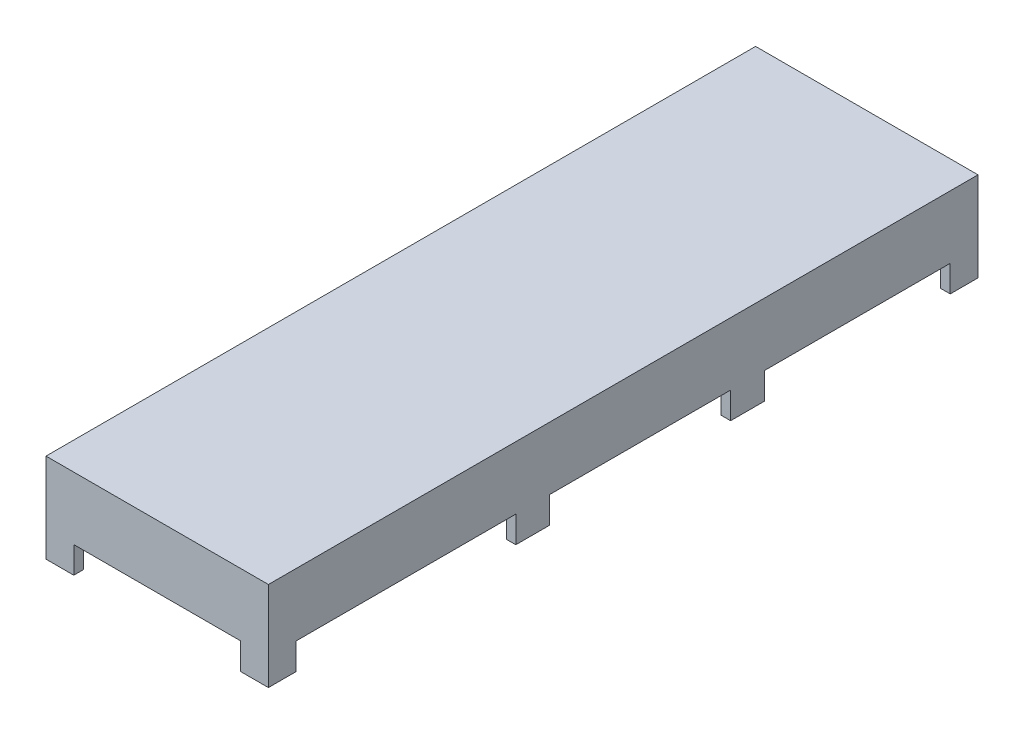
SolidWorks part; units mm, degrees
note: The reader was unsure of these and kept them because the rebuilt part matched: shared geometry of "草图2<5>".
material "6061 合金"
ref_plane "前视基准面" through (0, 0, 0) normal (0, 0, 1) x (1, 0, 0)
ref_plane "上视基准面" through (0, 0, 0) normal (0, 1, 0) x (1, 0, 0)
ref_plane "右视基准面" through (0, 0, 0) normal (1, 0, 0) x (0, 0, -1)
other "Configuration Table"
sketch "草图2" plane through (0, 0, 0) normal (0, 1, 0) x (1, 0, 0)
  line L1 (0, 0) -> (9.215, 0)
  line L2 (0, 0) -> (0, 29.4)
  line L3 (0, 29.4) -> (9.215, 29.4)
  line L4 (9.215, 0) -> (9.215, 29.4)
  line L5 (0, 0) -> (9.215, 0)
  line L6 (0, 0) -> (0, 29.4)
  line L7 (0, 29.4) -> (9.215, 29.4)
  line L8 (9.215, 0) -> (9.215, 29.4)
  line L9 (0.4, 0.4) -> (8.82, 0.4)
  line L10 (0.4, 0.4) -> (0.4, 29)
  line L11 (0.4, 29) -> (8.82, 29)
  line L12 (8.82, 0.4) -> (8.82, 29)
  dimension "D1" = 9.215
  dimension "D2" = 29.4
extrude "凸台-拉伸1" add sketch "草图2" along normal blind 3.7 contours L3 L4 L1 L2
extrude "切除-拉伸2" cut sketch "草图2<5>" along normal blind 3.3 contours L9 L12 L11 L10
sketch "草图2<5>" plane through (0, 0, 0) normal (0, 1, 0) x (1, 0, 0) same geometry as "草图2"
sketch "草图3" plane through (0, 0, 0) normal (0, 0, 1) x (1, 0, 0)
  line L0 (0, 0) -> (1.15, 0)
  line L1 (0, 0) -> (9.215, 0) construction
  line L2 (1.15, 0) -> (1.15, 1.1)
  line L4 (9.215, 0) -> (8.065, 0)
  line L5 (8.065, 0) -> (8.065, 1.1)
  line L6 (8.065, 1.1) -> (1.15, 1.1)
  line L7 (1.15, 0) -> (8.065, 0)
  dimension "D1" = 1.15
  dimension "D2" = 1.15
  dimension "D3" = 1.1
extrude "切除-拉伸7" cut sketch "草图3" against normal blind 0.4 and the other way through all contours L2 L6 L5
sketch "草图8" plane through (0, 0, -29.4) normal (0, 0, -1) x (-1, 0, 0)
  line L1 (-9.215, 0) -> (-8.065, 0)
  line L2 (-8.065, 0) -> (-8.065, 1.1)
  line L3 (-8.065, 1.1) -> (-1.15, 1.1)
  line L4 (-1.15, 1.1) -> (-1.15, 0)
  line L5 (-1.15, 0) -> (0, 0)
extrude "切除-拉伸11" cut sketch "草图8" against normal blind 0.4 and the other way through all flip side to cut contours L1 L2 L3 L4 L5
sketch "草图11" plane through (9.215, 0, 0) normal (1, 0, 0) x (0, 0, -1)
  line L0 (0, 0) -> (1.15, 0)
  line L1 (0, 0) -> (29.4, 0) construction
  line L2 (1.15, 0) -> (1.15, 1.1)
  line L3 (1.15, 1.1) -> (10.25, 1.1)
  line L4 (10.25, 1.1) -> (10.25, 0)
  line L5 (10.25, 0) -> (11.65, 0)
  line L6 (11.65, 0) -> (11.65, 1.1)
  line L7 (11.65, 1.1) -> (19.15, 1.1)
  line L8 (19.15, 1.1) -> (19.15, 0)
  line L9 (19.15, 0) -> (20.55, 0)
  line L10 (20.55, 0) -> (20.55, 1.1)
  line L11 (20.55, 1.1) -> (28.25, 1.1)
  line L12 (28.25, 1.1) -> (28.25, 0)
  line L13 (28.25, 0) -> (29.4, 0)
  dimension "D1" = 1.15
  dimension "D2" = 1.4
  dimension "D3" = 1.4
  dimension "D4" = 1.15
  dimension "D5" = 9.1
  dimension "D6" = 7.7
  dimension "D7" = 1.1
  dimension "D8" = 1.1
  dimension "D9" = 1.1
sketch "草图14" plane through (0, 0, 0) normal (-1, 0, 0) x (0, 0, 1)
  line L0 (-29.4, 0) -> (-28.25, 0)
  line L1 (-28.25, 0) -> (-28.25, 1.1)
  line L2 (-28.25, 1.1) -> (-20.55, 1.1)
  line L3 (-20.55, 1.1) -> (-20.55, 0)
  line L4 (-20.55, 0) -> (-19.15, 0)
  line L5 (-19.15, 0) -> (-19.15, 1.1)
  line L6 (-19.15, 1.1) -> (-11.65, 1.1)
  line L7 (-11.65, 1.1) -> (-11.65, 0)
  line L8 (-11.65, 0) -> (-10.25, 0)
  line L9 (-10.25, 0) -> (-10.25, 1.1)
  line L10 (-10.25, 1.1) -> (-1.15, 1.1)
  line L11 (-1.15, 1.1) -> (-1.15, 0)
  line L12 (-1.15, 0) -> (0, 0)
  line L13 (-28.25, 0) -> (-20.55, 0)
  line L14 (-19.15, 0) -> (-11.65, 0)
  line L15 (-10.25, 0) -> (-1.15, 0)
extrude "切除-拉伸12" cut sketch "草图14" against normal blind 10 contours L1 L2 L3 L13 | L9 L10 L11 L15 | L7 L6 L5 L14
